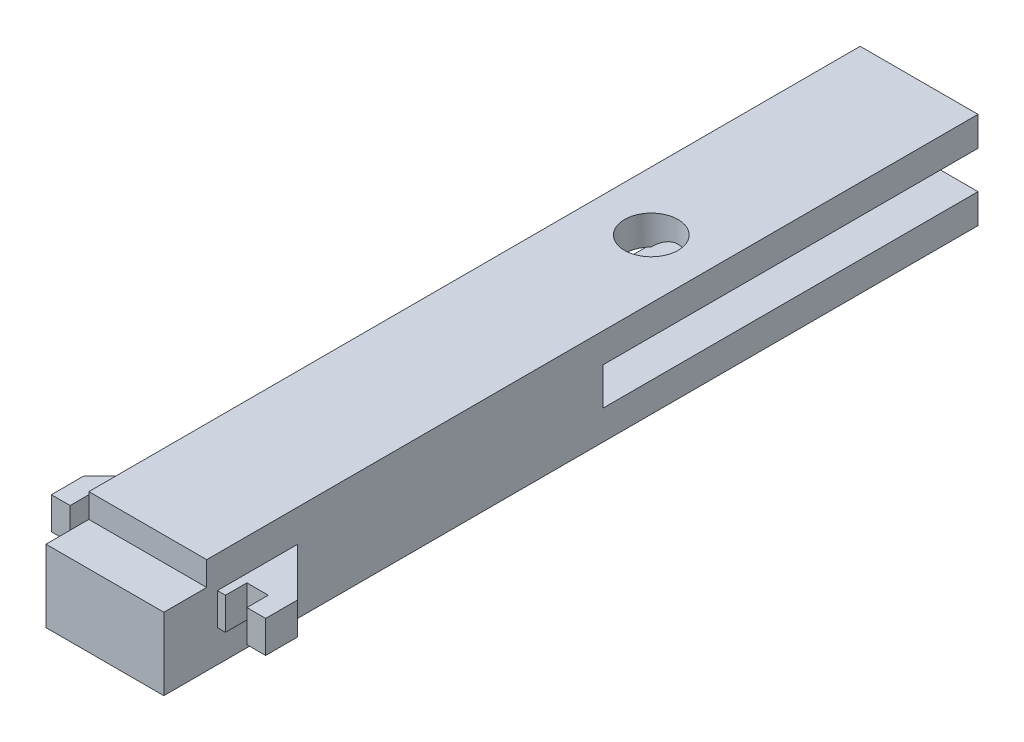
SolidWorks part; units mm, degrees
ref_plane "Front Plane" through (0, 0, 0) normal (0, 0, 1) x (1, 0, 0)
ref_plane "Top Plane" through (0, 0, 0) normal (0, 1, 0) x (1, 0, 0)
ref_plane "Right Plane" through (0, 0, 0) normal (1, 0, 0) x (0, 0, -1)
sketch "Sketch1" plane through (0, 0, 0) normal (0, 1, 0) x (1, 0, 0)
  line L1 (-5.5, 38) -> (5.5, 38)
  line L2 (-5.5, 38) -> (-5.5, -38)
  line L3 (-5.5, -38) -> (5.5, -38)
  line L4 (5.5, 38) -> (5.5, -38)
  line L5 (-5.5, 38) -> (5.5, -38) construction
  line L6 (-5.5, -38) -> (5.5, 38) construction
  point P0 (0, 0)
  dimension "D1" = 76
  dimension "D2" = 11
extrude "Boss-Extrude1" add sketch "Sketch1" along normal blind 9
ref_plane "Plane1" through (0, 0, 0) normal (-1, 0, 0) x (0, 0, 1)
sketch "Sketch3" plane through (0, 0, 0) normal (-1, 0, 0) x (0, 0, 1)
  line L0 (-38, 4.5) -> (27, 4.5)
  line L2 (38, 9) -> (38, 0) construction
  line L3 (-38, 9) -> (-38, 0) construction
  line L4 (31, 0.5) -> (31, 0)
  line L5 (-38, 0) -> (38, 0) construction
  arc A1 (31, 0.5) -> (27, 4.5) centre (27, 0.5) ccw
  point P9 (31, 4.5)
  point P14 (-38, 4.5)
  dimension "D1" = 4
  dimension "D2" = 7
sketch "Sketch4" plane through (0, 0, -38) normal (0, 0, -1) x (-1, 0, 0)
  line L0 (-5.5, 9) -> (-5.5, 0) construction
  line L1 (0, -55.5125) -> (0, 55.5125) construction
  circle A0 centre (0, 4.5) radius 2.5
  point P8 (-5.5, 4.5)
  dimension "D1" = 5
sweep "Cut-Sweep2" cut profiles "Sketch4" path "Sketch3"
sketch "Sketch5" plane through (-5.5, 0, 0) normal (-1, 0, 0) x (0, 0, 1)
  line L0 (38, 9) -> (38, 0) construction
  line L1 (30, 6) -> (33, 6)
  line L2 (30, 6) -> (30, 3)
  line L3 (30, 3) -> (33, 3)
  line L4 (33, 6) -> (33, 3)
  line L5 (30, 6) -> (33, 3) construction
  line L6 (30, 3) -> (33, 6) construction
  point P0 (31.5, 4.5)
  point P7 (38, 4.5)
  point P8 (33, 4.5)
  dimension "D1" = 3
  dimension "D2" = 5
extrude "Boss-Extrude2" add sketch "Sketch5" along normal blind 4.5
ref_plane "Plane2" through (0, 0, 0) normal (-1, 0, 0) x (0, 0, 1)
mirror "Mirror1" about plane through (0, 0, 0) normal (-1, 0, 0) of "Boss-Extrude2"
sketch "Sketch6" plane through (0, 0, 33) normal (0, 0, 1) x (1, 0, 0)
  line L1 (-8.25, 6) -> (-6.25, 6)
  line L2 (-8.25, 6) -> (-8.25, 3)
  line L3 (-8.25, 3) -> (-6.25, 3)
  line L4 (-6.25, 6) -> (-6.25, 3)
  line L5 (-8.25, 6) -> (-6.25, 3) construction
  line L6 (-8.25, 3) -> (-6.25, 6) construction
  line L7 (-10, 3) -> (-5.5, 3) construction
  line L8 (-5.5, 3) -> (-5.5, 6) construction
  point P0 (-7.25, 4.5)
  dimension "D1" = 0.75
  dimension "D2" = 2
extrude "Cut-Extrude2" cut sketch "Sketch6" against normal offset from surface (2 mm away) 1 up to face at (-7.75, 4.5, 30)
mirror "Mirror2" about plane through (0, 0, 0) normal (-1, 0, 0) of "Cut-Extrude2"
sketch "Sketch7" plane through (0, 6, 0) normal (0, 1, 0) x (1, 0, 0)
  line L0 (-10, -30) -> (-5.5, -25.5)
  line L1 (-5.5, 38) -> (-5.5, -38) construction
  line L2 (-5.5, -25.5) -> (-5.5, -30)
  line L3 (-5.5, -30) -> (-10, -30)
extrude "Boss-Extrude3" add sketch "Sketch7" against normal up to surface (3 mm away) up to face at (-7.5, 3, 31.75)
mirror "Mirror3" about plane through (0, 0, 0) normal (-1, 0, 0) of "Boss-Extrude3"
sketch "Sketch10" plane through (0, 0, -38) normal (0, 0, -1) x (-1, 0, 0)
  line L0 (10, 6.25) -> (1.7146, 6.25) construction
  line L1 (-5.5, 6.25) -> (5.5, 6.25)
  line L2 (-5.5, 6.25) -> (-5.5, 2.75)
  line L3 (-5.5, 2.75) -> (5.5, 2.75)
  line L4 (5.5, 6.25) -> (5.5, 2.75)
  line L5 (-5.5, 6.25) -> (5.5, 2.75) construction
  line L6 (-5.5, 2.75) -> (5.5, 6.25) construction
  point P0 (0, 4.5)
  dimension "D2" = 11
extrude "Cut-Extrude5" cut sketch "Sketch10" against normal blind 35
sketch "Sketch11" plane through (0, 9, 0) normal (0, 1, 0) x (1, 0, 0)
  line L0 (5.5, 38) -> (-5.5, 38) construction
  circle A0 centre (0, 13) radius 2.5
  dimension "D1" = 5
  dimension "D2" = 25
extrude "Cut-Extrude6" cut sketch "Sketch11" against normal up to next
sketch "Sketch12" plane through (0, 0, 38) normal (0, 0, 1) x (1, 0, 0)
  line L1 (-5.5, 9) -> (5.5, 9)
  line L2 (-5.5, 9) -> (-5.5, 6.75)
  line L3 (-5.5, 6.75) -> (5.5, 6.75)
  line L4 (5.5, 9) -> (5.5, 6.75)
  line L5 (5.5, 3) -> (5.5, 6) construction
  dimension "D1" = 2.25
  dimension "D2" = 11
extrude "Cut-Extrude9" cut sketch "Sketch12" against normal blind 4
